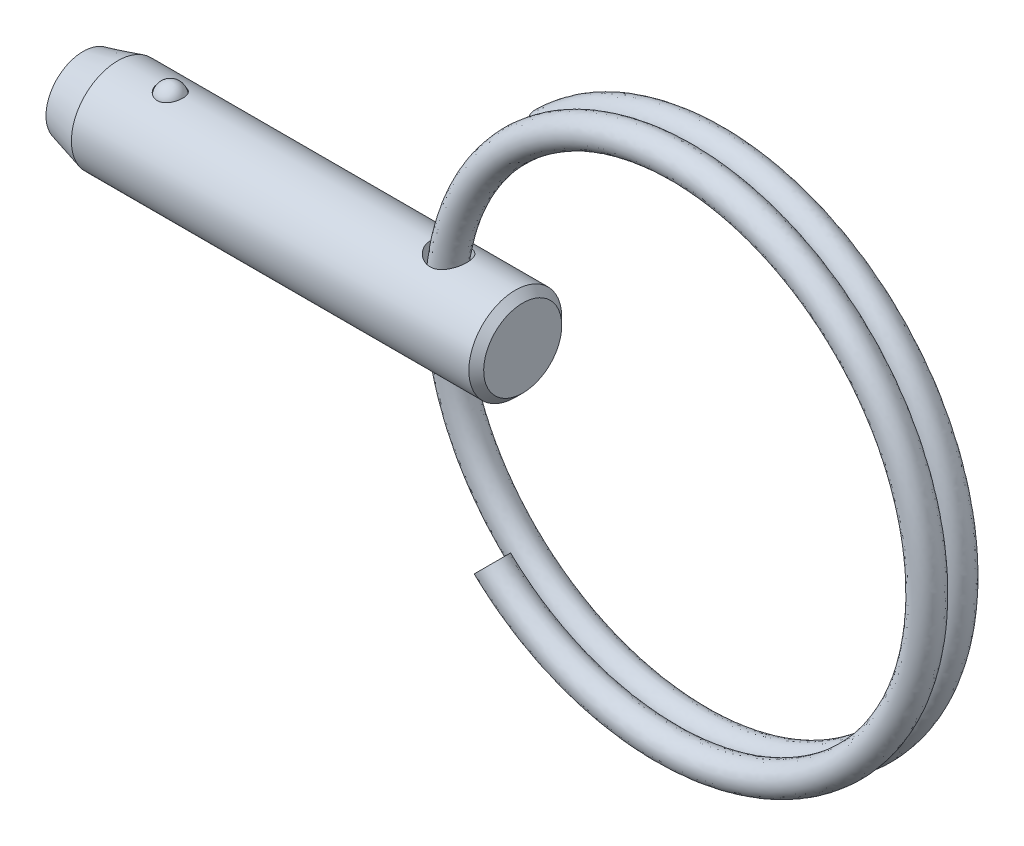
SolidWorks part; units mm, degrees
ref_plane "Front" through (0, 0, 0) normal (0, 0, 1) x (1, 0, 0)
ref_plane "Top" through (0, 0, 0) normal (0, 1, 0) x (1, 0, 0)
ref_plane "Right" through (0, 0, 0) normal (1, 0, 0) x (0, 0, -1)
sketch "Sketch1" plane through (0, 0, 0) normal (0, 0, 1) x (1, 0, 0)
  line L0 (11.2649, 2.0003) -> (10.8839, 2.3812)
  line L1 (10.8839, 2.3812) -> (11.2649, 2.3812) construction
  line L4 (11.2649, 2.0003) -> (11.2649, 0)
  line L5 (11.2649, 2.3812) -> (11.2649, 2.0003) construction
  line L16 (10.8839, 2.3812) -> (-9.4875, 2.3812)
  line L17 (-11.2649, 2.3812) -> (-11.2649, 1.905) construction
  line L19 (-9.4875, 2.3812) -> (-11.2649, 2.3812) construction
  line L22 (-11.2649, -2.3813) -> (-9.4875, -2.3812) construction
  line L23 (-6.7975, 2.1431) -> (-6.7975, -2.1431) construction
  line L24 (-11.2649, 0) -> (11.2649, 0)
  line L27 (11.2649, 0) -> (13.2652, 0) construction
  line L29 (-11.2649, 0) -> (-11.2649, -1.905) construction
  line L36 (6.5151, 0) -> (6.5151, 2.3812) construction
  line L37 (-11.2649, 1.905) -> (-11.2649, 0)
  line L38 (-9.4875, -2.3812) -> (11.2649, -2.3813) construction
  line L39 (-11.2649, -1.905) -> (-11.2649, -2.3813) construction
  line L40 (-9.4875, 2.3812) -> (-11.2649, 1.905)
  line L42 (-9.4875, -2.3812) -> (-11.2649, -1.905) construction
  line L43 (-9.4875, 2.3812) -> (-9.4875, -2.3812) construction
  circle A2 centre (-6.7975, 2.1431) radius 0.6572 construction
  point P35 (-6.1849, 2.3812)
  dimension "A1" = 15
revolve "Revolve1" add sketch "Sketch1" angle 360 about L27
sketch "Sketch2" plane through (0, 0, 0) normal (0, 0, 1) x (1, 0, 0)
  line L0 (-6.1148, 2.1431) -> (-7.4801, 2.1431)
  line L1 (-6.7975, 2.8003) -> (-6.7975, 2.8257) construction
  line L2 (-6.1148, 2.1431) -> (-4.7496, 2.1431) construction
  circle A0 centre (-6.7975, 2.1431) radius 0.6572 construction
  circle A1 centre (-6.7975, 2.1431) radius 0.6572 construction
  arc A2 (-7.4801, 2.1431) -> (-6.1148, 2.1431) centre (-6.7975, 2.1431) cw
  dimension "D1" = 0.0254
revolve "Cut-Revolve1" cut sketch "Sketch2" angle 360 about L2
sketch "Sketch3" plane through (0, 0, 0) normal (0, 0, 1) x (1, 0, 0)
  line L0 (-6.1402, 2.1431) -> (-7.4547, 2.1431)
  line L1 (-6.1402, 2.1431) -> (-4.8258, 2.1431) construction
  circle A0 centre (-6.7975, 2.1431) radius 0.6572 construction
  arc A1 (-6.1402, 2.1431) -> (-7.4547, 2.1431) centre (-6.7975, 2.1431) ccw
revolve "Revolve2" add sketch "Sketch3" angle 360 about L1
sketch "Sketch4" plane through (0, 0, 0) normal (0, 0, 1) x (1, 0, 0)
  line L1 (7.4676, -2.3812) -> (8.4201, -2.3812)
  line L2 (7.4676, -2.3812) -> (7.4676, 2.3812)
  line L3 (7.4676, 2.3812) -> (8.4201, 2.3812)
  line L4 (8.4201, -2.3812) -> (8.4201, 2.3812)
  line L5 (7.4676, -2.3812) -> (7.4676, -3.3338) construction
  line L6 (8.4201, 2.3812) -> (11.2649, 2.3812) construction
  line L8 (6.5151, -2.3812) -> (6.5151, 2.3812) construction
  line L9 (6.5151, 0) -> (7.4676, 0) construction
  line L11 (7.4676, 0) -> (8.4201, 0) construction
  line L12 (10.8839, 2.3812) -> (-9.4875, 2.3812) construction
  line L14 (-9.4875, -2.3812) -> (11.2649, -2.3812) construction
  dimension "D1" = 1.905
revolve "Cut-Revolve2" cut sketch "Sketch4" angle 360 about L2
sketch "Sketch5" plane through (0, 0, 0) normal (0, 0, 1) x (1, 0, 0)
  line L0 (0, 0) -> (6.5856, 0) construction
  line L1 (6.5856, 0) -> (6.5856, 2.3812) construction
  line L2 (10.8839, 2.3812) -> (-9.4875, 2.3812) construction
  line L3 (20.0476, 0) -> (33.5096, 0) construction
  line L4 (8.4201, 2.3812) -> (8.3496, 2.3812) construction
  line L5 (7.4676, 2.3812) -> (8.4201, 2.3812) construction
  line L6 (6.7979, 2.3812) -> (6.7979, -2.3812) construction
  line L7 (6.5856, 2.3812) -> (6.5151, 2.3812) construction
  line L8 (7.4676, -2.3812) -> (8.4201, -2.3812) construction
  line L9 (6.7979, -2.3812) -> (8.4201, -2.3812) construction
  line L10 (6.5856, 0) -> (20.0476, 0) construction
  line L12 (8.3496, 2.3812) -> (6.7979, 2.3812) construction
  line L13 (20.0476, 11.938) -> (20.0476, 13.462) construction
  circle A0 centre (20.0476, 0) radius 13.462
  circle A1 centre (20.0476, 0) radius 11.938 construction
  circle A2 centre (20.0476, 0) radius 12.7 construction
  point P26 (20.0476, 12.7)
curve "Helix/Spiral1" pitch 1.5494 height 1.3557 radius 13.462 left hand yes centre (20.0476, 0, 0) axis (0, 0, -1) start towards (1, 0, 0)
sketch "Sketch6" plane through (114.0038, 0, 0) normal (0, 1, 0) x (0, 0, -1)
  line L0 (0, 105.8942) -> (0, 106.6562) construction
  line L1 (0, 106.6562) -> (0, 107.4182) construction
  circle A0 centre (0, 106.6562) radius 0.762
  dimension "D1" = 1.524
sketch "Sketch7" plane through (0, 0, 0) normal (0, 0, 1) x (1, 0, 0)
  circle A0 centre (20.0476, 0) radius 13.462 construction
  circle A1 centre (20.0476, 0) radius 13.462
curve "Helix/Spiral2" pitch 1.5494 height 1.3557 radius 13.462 left hand yes centre (20.0476, 0, 0) axis (0, 0, 1) start towards (1, 0, 0)
sweep "Sweep1" add profiles "Sketch6" path "Helix/Spiral1"
sweep "Sweep2" add profiles "Sketch6<2>" path "Helix/Spiral2"
sketch "Sketch6<2>" plane through (114.0038, 0, 0) normal (0, 1, 0) x (0, 0, -1) same geometry as "Sketch6"
equation "\"D12@Sketch1\"=\"A@Sketch1\" * 0.80"
equation "\"D2@Sketch1\"=\"A@Sketch1\" * 0.9"
equation "\"D1@Sketch4\" = \"A@Sketch1\" / 2.5"
equation "\"Ring OD@Sketch5\" = \"R Ring Dia@Sketch5\" * 0.06"
equation "\"D4@Helix/Spiral1\"=\"Ring OD@Sketch5\" + 0.001"
equation "\"D1@Sketch6\"=\"Ring OD@Sketch5\""
equation "\"D4@Helix/Spiral2\" = \"D4@Helix/Spiral1\""
equation "\"D5@Helix/Spiral2\" = \"D5@Helix/Spiral1\""
